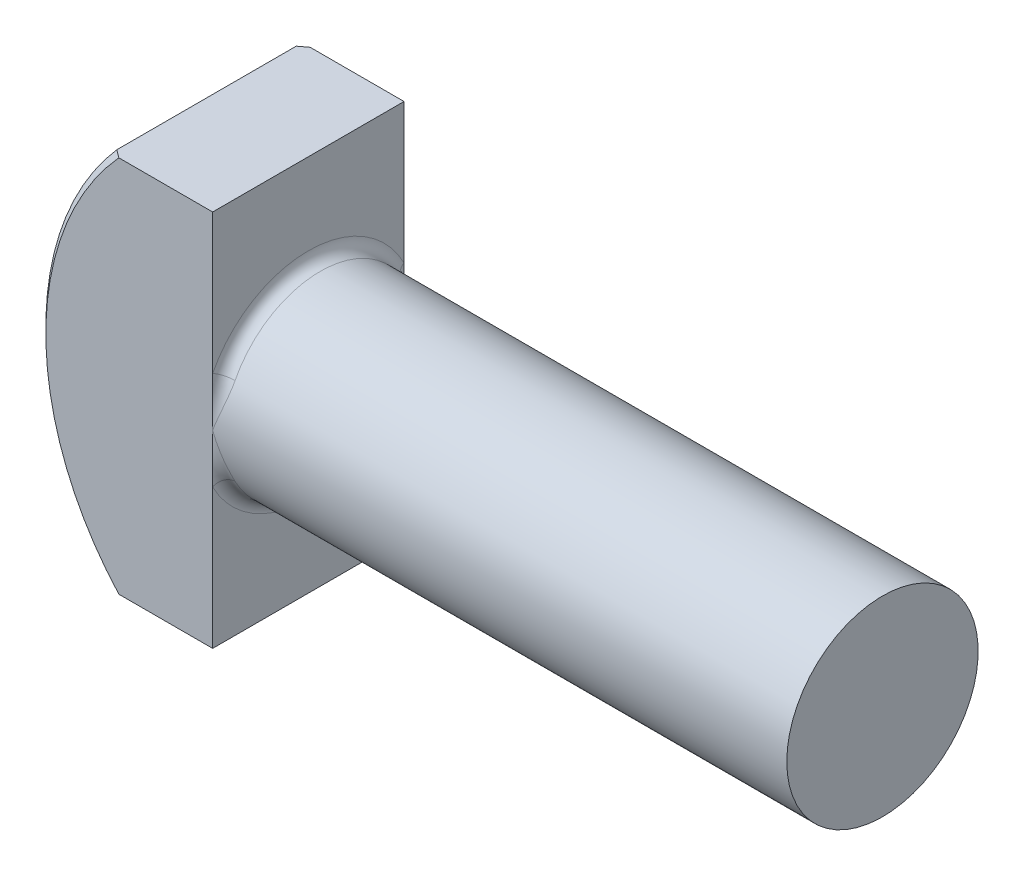
SolidWorks part; units mm, degrees
ref_plane "Plane1" through (0, 0, 0) normal (0, 0, 1) x (1, 0, 0)
ref_plane "Plane2" through (0, 0, 0) normal (0, 1, 0) x (1, 0, 0)
ref_plane "Plane3" through (0, 0, 0) normal (1, 0, 0) x (0, 0, -1)
sketch "Sketch1" plane through (0, 0, 0) normal (0, 0, 1) x (1, 0, 0)
  line L1 (9.4211, 25.0825) -> (22.9362, 25.0825)
  line L2 (22.9362, 25.0825) -> (22.9362, -25.0825)
  line L3 (22.9362, -25.0825) -> (9.4211, -25.0825)
  arc A0 (9.4211, 25.0825) -> (9.4211, -25.0825) centre (38.1, 0) ccw
  dimension "D1" = 25.0825
  dimension "D2" = 38.1
  dimension "Head_ht" = 22.9362
sketch "BodySke" plane through (0, 0, 0) normal (0, 0, 1) x (1, 0, 0)
  line L0 (99.1362, 0) -> (22.9362, 0)
  line L1 (22.9362, 12.7) -> (99.1362, 12.7)
  line L2 (22.9362, -12.7) -> (99.1362, -12.7) construction
  line L3 (99.1362, 12.7) -> (99.1362, 0)
  line L4 (22.9362, 0) -> (22.9362, 12.7)
  line L5 (25.0444, 15.875) -> (25.0444, -3.175) construction
  line L6 (0, 0) -> (107.95, 0) construction
  line L7 (67.3862, 15.875) -> (67.3862, -3.175) construction
  dimension "D1" = 22.9362
  dimension "Length" = 76.2
  dimension "Diameter" = 25.4
extrude "BaseHead" add sketch "Sketch1" along normal mid plane 25.4
revolve "Body" add sketch "BodySke" angle 360 about L6
cosmetic thread "ThreadCosmetic" [suppressed] parameters "Thread_length"=31.75, "Thread_minor"=21.6154
chamfer "HeadChamfer" distance 0.7937 angle 45 2 edges at (0, 0, 12.7) (0, 0, -12.7)
fillet "HeadFillet" radius 1.5748 2 edges at (22.9362, -12.7, 0) (22.9362, 12.7, 0)
sketch "ThdSchSke" plane through (0, 0, 0) normal (0, 0, 1) x (1, 0, 0)
  line L0 (67.3862, -10.8077) -> (66.0612, -12.7)
  line L1 (67.3862, -10.8077) -> (68.7112, -12.7)
  line L2 (68.7112, -12.7) -> (68.7112, -15.875)
  line L3 (-3.175, 0) -> (5.1513, 0) construction
  line L5 (68.7112, -15.875) -> (66.0612, -15.875)
  line L6 (66.0612, -15.875) -> (66.0612, -12.7)
  dimension "Thread_minor" = 21.6154
  dimension "Diameter" = 25.4
  dimension "Start" = 67.3862
revolve "ThreadSchematic" [suppressed] cut sketch "ThdSchSke" angle 360 about L3
pattern_linear "ThdSchPat" [suppressed]
equation "\"D1@Sketch1\" = \"Head_len@Sketch1\" / 2"
equation "\"D2@Sketch1\" = \"Head_radius@Sketch1\""
equation "\"D1@BodySke\" = \"Head_ht@Sketch1\""
equation "\"D1@BaseHead\" = \"Diameter@BodySke\""
equation "\"Thread_length@ThreadCosmetic\" = ((sgn( (\"Length@BodySke\" - \"Advance@BodySke\" ) - \"Thread_nom@BodySke\" )-1)*( (\"Length@BodySke\" - \"Advance@BodySke\" ) - \"Thread_nom@BodySke\" ))/-2+ \"Thread_nom@BodySke\""
equation "\"Thread_minor@ThdSchSke\" = \"Thread_minor@ThreadCosmetic\""
equation "\"Diameter@ThdSchSke\" = \"Diameter@BodySke\""
equation "\"Overcut@ThdSchSke\" = \"Diameter@BodySke\" * 1.25"
equation "\"Start@ThdSchSke\" = \"Head_ht@Sketch1\" + \"Length@BodySke\" - \"Thread_length@ThreadCosmetic\"  '---Non-countersunk---"
equation "\"Num_threads@ThdSchPat\" = int( \"Thread_length@ThreadCosmetic\" / \"Advance@BodySke\" + 0.999 )  + 1"
equation "\"Advance@ThdSchPat\" = \"Thread_length@ThreadCosmetic\" /  (\"Num_threads@ThdSchPat\" - 1) 'relax it"
